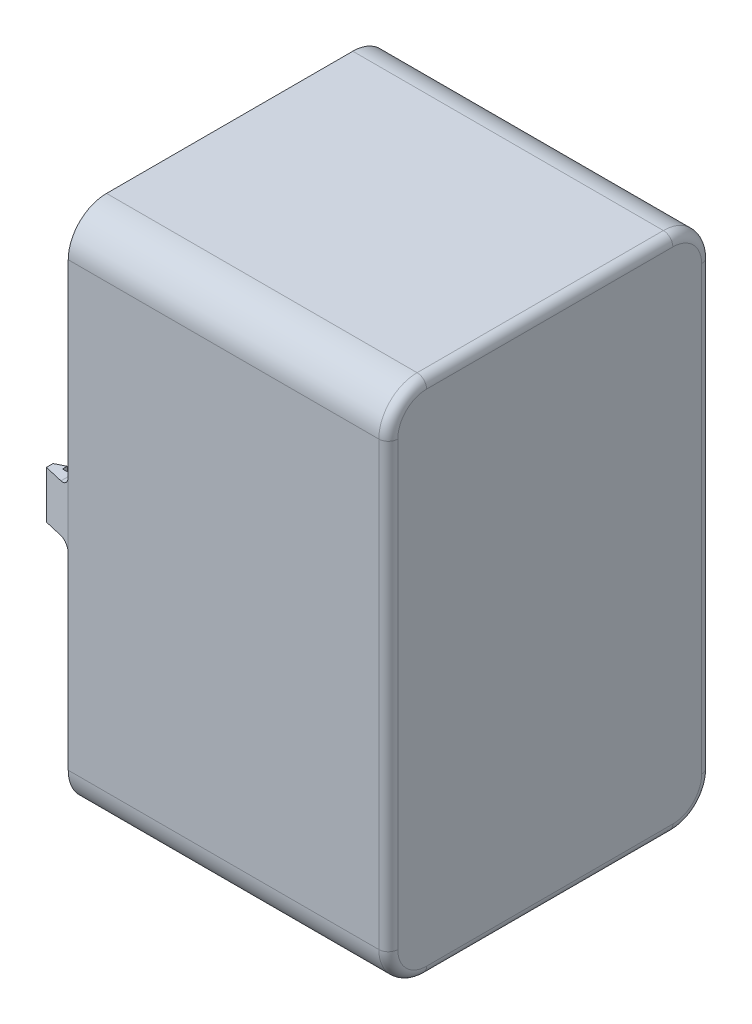
SolidWorks part; units mm, degrees
ref_plane "Top Plane" through (0, 0, 0) normal (0, 0, 1) x (1, 0, 0)
ref_plane "Right Plane" through (0, 0, 0) normal (0, 1, 0) x (1, 0, 0)
ref_plane "Front Plane" through (0, 0, 0) normal (1, 0, 0) x (0, 0, -1)
ref_axis "x-axis" through (-88.99, 0, 0) along (1, 0, 0)
ref_axis "y-axis" through (0, -55, 0) along (0, 1, 0)
ref_axis "z-axis" through (0, 0, 55) along (0, 0, -1)
sketch "Sketch2" plane through (0, 0, 0) normal (1, 0, 0) x (0, -1, 0)
  line L0 (-980.3227, 1369.3053) -> (-980.3227, 1357.3053) construction
  line L1 (-1019.3227, 1357.3053) -> (-1019.3227, 1369.3053) construction
  line L2 (-980.3227, 1357.3053) -> (-1019.3227, 1357.3053) construction
  line L3 (-1018.3227, 1369.3053) -> (-981.3227, 1369.3053) construction
  line L12 (-980.3227, 1369.3053) -> (-980.3227, 1357.3053)
  line L13 (-980.3227, 1357.3053) -> (-1019.3227, 1357.3053)
  line L14 (-1019.3227, 1357.3053) -> (-1019.3227, 1369.3053)
  line L15 (-1019.3227, 1369.3053) -> (-980.3227, 1369.3053)
  line L29 (-1027.1727, 1376.2903) -> (-1027.1727, 1350.3203)
  line L30 (-976.5127, 1380.3303) -> (-1023.1327, 1380.3303)
  line L31 (-972.4727, 1350.3203) -> (-972.4727, 1376.2903)
  line L32 (-1023.1327, 1346.2803) -> (-976.5127, 1346.2803)
  line L33 (-1027.1727, 1376.2903) -> (-1027.1727, 1350.3203)
  line L34 (-976.5127, 1380.3303) -> (-1023.1327, 1380.3303)
  line L35 (-972.4727, 1350.3203) -> (-972.4727, 1376.2903)
  line L36 (-1023.1327, 1346.2803) -> (-976.5127, 1346.2803)
  arc A20 (-1027.1727, 1350.3203) -> (-1023.1327, 1346.2803) centre (-1023.1327, 1350.3203) ccw
  arc A21 (-1023.1327, 1380.3303) -> (-1027.1727, 1376.2903) centre (-1023.1327, 1376.2903) ccw
  arc A22 (-972.4727, 1376.2903) -> (-976.5127, 1380.3303) centre (-976.5127, 1376.2903) ccw
  arc A23 (-976.5127, 1346.2803) -> (-972.4727, 1350.3203) centre (-976.5127, 1350.3203) ccw
  arc A24 (-1027.1727, 1350.3203) -> (-1023.1327, 1346.2803) centre (-1023.1327, 1350.3203) ccw
  arc A25 (-1023.1327, 1380.3303) -> (-1027.1727, 1376.2903) centre (-1023.1327, 1376.2903) ccw
  arc A26 (-972.4727, 1376.2903) -> (-976.5127, 1380.3303) centre (-976.5127, 1376.2903) ccw
  arc A27 (-976.5127, 1346.2803) -> (-972.4727, 1350.3203) centre (-976.5127, 1350.3203) ccw
  dimension "D1" = 1.5
extrude "Boss-Extrude2" add sketch "Sketch2" along normal blind 13 and the other way blind 19.75
sketch "Sketch3" plane through (13, 0, 0) normal (1, 0, 0) x (0, 1, 0)
  line L0 (972.4727, -1350.3203) -> (972.4727, -1376.2903) construction
  line L1 (976.5127, -1380.3303) -> (1023.1327, -1380.3303) construction
  line L2 (1027.1727, -1376.2903) -> (1027.1727, -1350.3203) construction
  line L3 (1023.1327, -1346.2803) -> (976.5127, -1346.2803) construction
  line L4 (972.4727, -1350.3203) -> (972.4727, -1376.2903)
  line L5 (976.5127, -1380.3303) -> (1023.1327, -1380.3303)
  line L7 (1027.1727, -1376.2903) -> (1027.1727, -1350.3203)
  line L13 (1023.1327, -1346.2803) -> (976.5127, -1346.2803)
  arc A0 (976.5127, -1346.2803) -> (972.4727, -1350.3203) centre (976.5127, -1350.3203) ccw construction
  arc A1 (972.4727, -1376.2903) -> (976.5127, -1380.3303) centre (976.5127, -1376.2903) ccw construction
  arc A2 (1023.1327, -1380.3303) -> (1027.1727, -1376.2903) centre (1023.1327, -1376.2903) ccw construction
  arc A3 (1027.1727, -1350.3203) -> (1023.1327, -1346.2803) centre (1023.1327, -1350.3203) ccw construction
  arc A4 (976.5127, -1346.2803) -> (972.4727, -1350.3203) centre (976.5127, -1350.3203) ccw
  arc A6 (972.4727, -1376.2903) -> (976.5127, -1380.3303) centre (976.5127, -1376.2903) ccw
  arc A7 (1023.1327, -1380.3303) -> (1027.1727, -1376.2903) centre (1023.1327, -1376.2903) ccw
  arc A13 (1027.1727, -1350.3203) -> (1023.1327, -1346.2803) centre (1023.1327, -1350.3203) ccw
extrude "Boss-Extrude3" add sketch "Sketch3" along normal blind 1
sketch "Sketch6" plane through (-19.75, 0, 0) normal (-1, 0, 0) x (0, -1, 0)
  line L22 (-972.4727, -1363.3053) -> (-1027.1727, -1363.3053) construction
  line L23 (-972.4727, -1350.3203) -> (-972.4727, -1376.2903) construction
  line L24 (-1027.1727, -1376.2903) -> (-1027.1727, -1350.3203) construction
  line L26 (-1025.7727, -1350.3203) -> (-1025.7727, -1376.2903)
  line L27 (-1023.1327, -1378.9303) -> (-976.5127, -1378.9303)
  line L28 (-973.8727, -1376.2903) -> (-973.8727, -1350.3203)
  line L29 (-976.5127, -1347.6803) -> (-1023.1327, -1347.6803)
  arc A32 (-1023.1327, -1347.6803) -> (-1025.7727, -1350.3203) centre (-1023.1327, -1350.3203) ccw
  arc A33 (-1025.7727, -1376.2903) -> (-1023.1327, -1378.9303) centre (-1023.1327, -1376.2903) ccw
  arc A34 (-976.5127, -1378.9303) -> (-973.8727, -1376.2903) centre (-976.5127, -1376.2903) ccw
  arc A35 (-973.8727, -1350.3203) -> (-976.5127, -1347.6803) centre (-976.5127, -1350.3203) ccw
  point P8 (-1025.7727, -1363.3053)
  point P9 (-999.8227, -1378.9303)
  point P10 (-999.8227, -1363.3053)
  dimension "D3" = 2.64
  dimension "D1" = 31.25
  dimension "D2" = 51.9
extrude "Cut-Extrude1" cut sketch "Sketch6" against normal offset from surface (19.727 mm away) 0.1 offset beyond the face yes
ref_plane "Plane1" through (0, 999.8227, 0) normal (0, -1, 0) x (-1, 0, 0)
ref_plane "Plane2" through (0, 0, -1363.3053) normal (0, 0, -1) x (-1, 0, 0)
sketch "Sketch10" plane through (0, 999.8227, 0) normal (0, -1, 0) x (-1, 0, 0)
  line L22 (19.75, 1346.2803) -> (19.75, 1347.6803)
  line L23 (19.75, 1347.6803) -> (21.75, 1347.6803)
  line L24 (21.75, 1347.6803) -> (21.75, 1348.1803)
  line L25 (21.75, 1348.1803) -> (22.75, 1347.6803)
  line L26 (22.75, 1347.6803) -> (22.75, 1346.9803)
  line L27 (22.75, 1346.9803) -> (19.75, 1346.2803)
  line L28 (19.75, 1346.2803) -> (19.75, 1350.3203) construction
  line L30 (19.75, 1346.2803) -> (19.75, 1350.3203) construction
  line L31 (0.023, 1347.6803) -> (19.75, 1347.6803) construction
  point P6 (0, 0)
  point P7 (19.75, 1346.9803)
  point P8 (0, 0)
  point P9 (27.62, -1.5)
  point P12 (24, -0.5115)
  point P13 (21, -1.5)
  point P14 (21, -0.3671)
  point P15 (21, -0.3621)
  point P20 (0, 0)
  dimension "D2" = 3
  dimension "D3" = 1
  dimension "D1" = 0.5
ref_axis "Axis1" through (0, 999.8227, -1344.5778) along (0, 0, -1)
extrude "Clip Edge" add sketch "Sketch10" along normal mid plane 5
mirror "Mirror1" about plane through (0, 0, -1363.3053) normal (0, 0, -1) of "Clip Edge"
fillet "Fillet1" radius 1 20 edges at (14, 973.656, -1379.147) (14, 972.4727, -1363.3053) (14, 973.656, -1347.4636) (14, 999.8227, -1346.2803) (14, 1025.9894, -1347.4636) (14, 1027.1727, -1363.3053) (14, 1025.9894, -1379.147) (13, 999.8227, -1357.3053) (13, 980.3227, -1363.3053) (13, 999.8227, -1369.3053) (13, 1019.3227, -1363.3053) (14, 999.8227, -1380.3303) (-0.023, 999.8227, -1369.3053) (-0.023, 980.3227, -1363.3053) (-0.023, 999.8227, -1357.3053) (-0.023, 1019.3227, -1363.3053) (-19.75, 997.3227, -1379.6303) (-19.75, 997.3227, -1346.9803) (-19.75, 1002.3227, -1346.9803) (-19.75, 1002.3227, -1379.6303)
